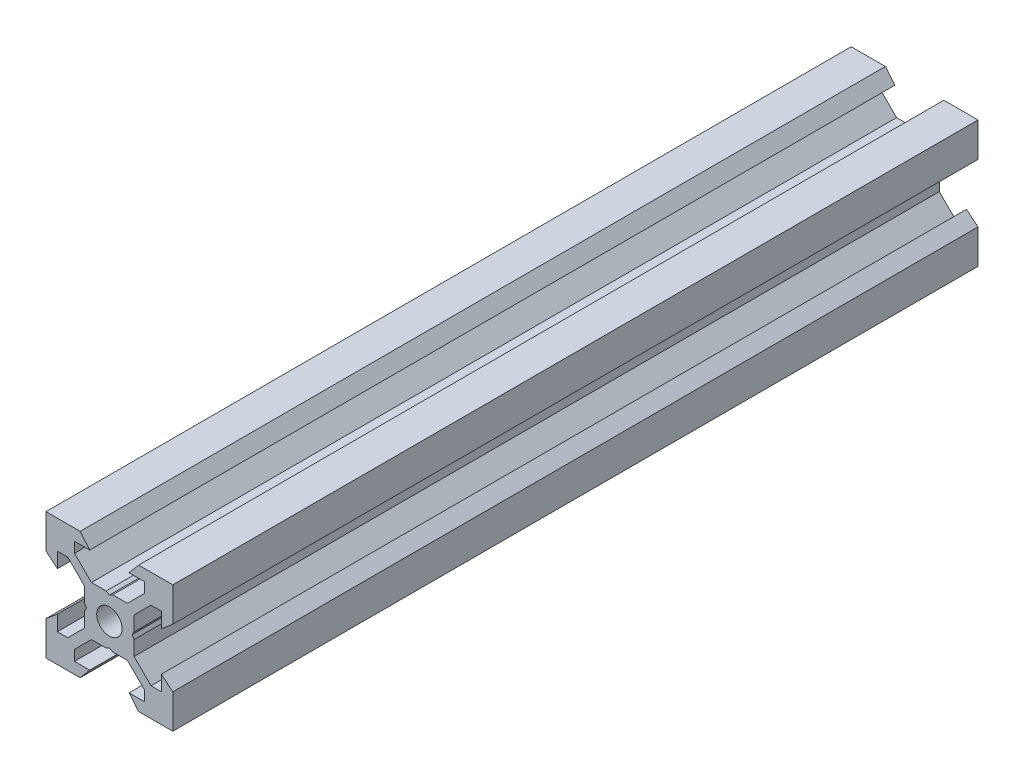
SolidWorks part; units mm, degrees
ref_plane "Front Plane" through (0, 0, 0) normal (0, 0, 1) x (1, 0, 0)
ref_plane "Top Plane" through (0, 0, 0) normal (0, 1, 0) x (1, 0, 0)
ref_plane "Right Plane" through (0, 0, 0) normal (1, 0, 0) x (0, 0, -1)
sketch "Sketch1" plane through (0, 0, 0) normal (0, 0, 1) x (1, 0, 0)
  line L0 (10, 10) -> (4.6104, 10) construction
  line L1 (10, 10) -> (10, 4.6104) construction
  line L2 (10, -10) -> (10, -4.6104) construction
  line L3 (10, -10) -> (4.6104, -10) construction
  line L4 (10, 10) -> (10, 4.6104)
  line L5 (6.5607, 5.5) -> (8.2, 5.5)
  line L6 (5.5, 8.2) -> (5.5, 6.5607)
  line L7 (10, 10) -> (4.6104, 10)
  line L8 (10, 10) -> (10, 4.6104)
  line L9 (6.5607, 5.5) -> (3.9, 2.8393)
  line L10 (5.5, 6.5607) -> (2.8393, 3.9)
  line L11 (10, 4.6104) -> (8.2, 3.1)
  line L12 (4.6104, 10) -> (3.1, 8.2)
  line L13 (8.2, 3.1) -> (8.2, 5.5)
  line L14 (3.1, 8.2) -> (5.5, 8.2)
  line L15 (-6.5607, 5.5) -> (-8.2, 5.5)
  line L16 (6.5607, -5.5) -> (8.2, -5.5)
  line L17 (3.1, -8.2) -> (5.5, -8.2)
  line L18 (8.2, -3.1) -> (8.2, -5.5)
  line L19 (4.6104, -10) -> (3.1, -8.2)
  line L20 (10, -4.6104) -> (8.2, -3.1)
  line L21 (0.5196, -3.9) -> (0, -3.6)
  line L22 (0.5196, 3.9) -> (0, 3.6)
  line L23 (3.6, 0) -> (3.9, -0.5196)
  line L24 (3.9, 0.5196) -> (3.6, 0)
  line L25 (3.9, 0.5196) -> (3.9, 2.8393)
  line L26 (2.8393, 3.9) -> (0.5196, 3.9)
  line L27 (3.9, -2.8393) -> (3.9, -0.5196)
  line L28 (2.8393, -3.9) -> (0.5196, -3.9)
  line L29 (5.5, -6.5607) -> (2.8393, -3.9)
  line L30 (6.5607, -5.5) -> (3.9, -2.8393)
  line L31 (10, -10) -> (10, -4.6104)
  line L32 (10, -10) -> (4.6104, -10)
  line L33 (5.5, -8.2) -> (5.5, -6.5607)
  line L34 (-6.5607, -5.5) -> (-8.2, -5.5)
  line L35 (10, -10) -> (10, -4.6104)
  line L36 (0, 0) -> (0, 8.2) construction
  line L37 (-10, -10) -> (-4.6104, -10) construction
  line L38 (-10, -10) -> (-10, -4.6104) construction
  line L39 (-10, 10) -> (-10, 4.6104) construction
  line L40 (-10, 10) -> (-4.6104, 10) construction
  line L41 (-10, -10) -> (-10, -4.6104)
  line L43 (-5.5, -8.2) -> (-5.5, -6.5607)
  line L44 (-10, -10) -> (-4.6104, -10)
  line L45 (-10, -10) -> (-10, -4.6104)
  line L46 (-6.5607, -5.5) -> (-3.9, -2.8393)
  line L47 (-5.5, -6.5607) -> (-2.8393, -3.9)
  line L48 (-2.8393, -3.9) -> (-0.5196, -3.9)
  line L49 (-3.9, -2.8393) -> (-3.9, -0.5196)
  line L50 (-2.8393, 3.9) -> (-0.5196, 3.9)
  line L51 (-3.9, 0.5196) -> (-3.9, 2.8393)
  line L52 (-3.9, 0.5196) -> (-3.6, 0)
  line L53 (-3.6, 0) -> (-3.9, -0.5196)
  line L54 (-0.5196, 3.9) -> (0, 3.6)
  line L55 (-0.5196, -3.9) -> (0, -3.6)
  line L56 (-10, -4.6104) -> (-8.2, -3.1)
  line L57 (-4.6104, -10) -> (-3.1, -8.2)
  line L58 (-8.2, -3.1) -> (-8.2, -5.5)
  line L59 (-3.1, -8.2) -> (-5.5, -8.2)
  line L60 (-10, -10) -> (10, -10) construction
  line L61 (-10, -10) -> (-10, 10) construction
  line L62 (-3.1, 8.2) -> (-5.5, 8.2)
  line L63 (-8.2, 3.1) -> (-8.2, 5.5)
  line L64 (-4.6104, 10) -> (-3.1, 8.2)
  line L65 (-10, 4.6104) -> (-8.2, 3.1)
  line L66 (-5.5, 6.5607) -> (-2.8393, 3.9)
  line L67 (-6.5607, 5.5) -> (-3.9, 2.8393)
  line L68 (-10, 10) -> (-10, 4.6104)
  line L69 (-10, 10) -> (-4.6104, 10)
  line L70 (-5.5, 8.2) -> (-5.5, 6.5607)
  line L71 (-10, 10) -> (10, 10) construction
  line L72 (-10, 10) -> (-10, 4.6104)
  line L73 (10, -10) -> (10, 10) construction
  line L74 (-10, -10) -> (10, 10) construction
  line L75 (-10, 10) -> (10, -10) construction
  circle A0 centre (0, 0) radius 2
  dimension "D7" = 4
  dimension "D1" = 20
  dimension "D2" = 5.3896
  dimension "D3" = 4.5
  dimension "D4" = 50
  dimension "D5" = 1.8
  dimension "D6" = 1.5104
  dimension "D8" = 5.5
  dimension "D9" = 120
  dimension "D10" = 0.3
  dimension "D11" = 2.3197
  dimension "D12" = 7.8
  dimension "D13" = 7.8
  dimension "D14" = 1.5
  dimension "D15" = 2.6607
extrude "Boss-Extrude1" add sketch "Sketch1" along normal mid plane 127 contours L70 L62 L64 L69 L68 L65 L63 L15 L67 L51 L52 L53 L49 L46 L34 L58 L56 L41 L44 L57 L59 L43 L47 L48 L55 L21 L28 L29 L33 L17 L19 L32 L31 L20 L18 L16 L30 L27 L23 L24 L25 L9 L5 L13 L11 L4 L7 L12 L14 L6 L10 region at (9.7172, 7.3052, 0)
